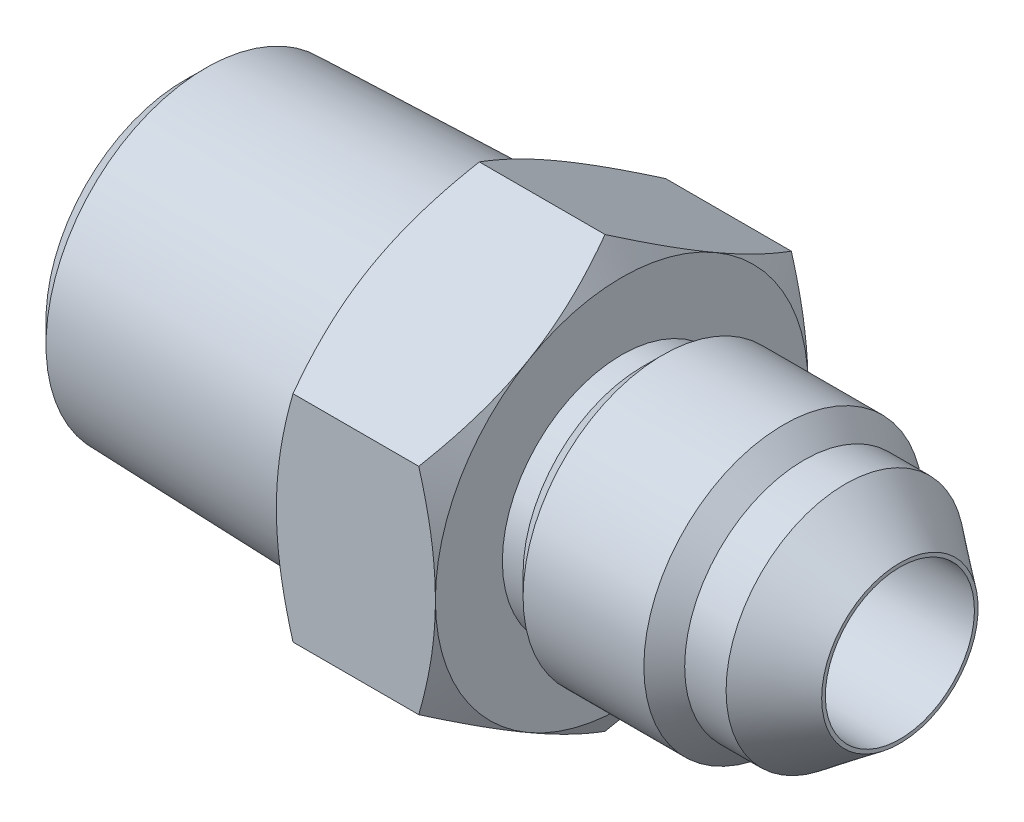
SolidWorks part; units mm, degrees
ref_plane "Front" through (0, 0, 0) normal (0, 0, 1) x (1, 0, 0)
ref_plane "Top" through (0, 0, 0) normal (0, 1, 0) x (1, 0, 0)
ref_plane "Right" through (0, 0, 0) normal (1, 0, 0) x (0, 0, -1)
sketch "Sketch6" plane through (0, 0, 0) normal (0, 0, 1) x (1, 0, 0)
  line L0 (-4.064, 8.5725) -> (-4.064, -8.5725) construction
  line L1 (18.288, 7.1438) -> (18.288, -7.1438) construction
  line L2 (-18.288, 0) -> (18.288, 0)
  line L4 (-18.288, 0) -> (-18.288, 7.1438)
  line L5 (-18.288, 7.1438) -> (18.288, 7.1438)
  line L6 (18.288, 0) -> (18.288, 7.1438)
  line L7 (-18.288, 3.81) -> (-18.288, -3.81) construction
  line L8 (-4.064, 10.287) -> (-4.064, -10.287) construction
  line L9 (4.064, 10.287) -> (4.064, -10.287) construction
  point P4 (4.064, 0)
  point P6 (-4.064, 0)
  dimension "Straight Dia" = 14.2875
  dimension "Length" = 36.576
  dimension "L1" = 14.224
  dimension "Pipe OD" = 17.145
  dimension "L2" = 14.224
  dimension "D1" = 7.62
  dimension "D2" = 20.574
revolve "Revolve3" add sketch "Sketch6" angle 360 about L2
sketch "Sketch14" plane through (18.288, 0, 0) normal (-1, 0, 0) x (0, 0, 1)
  circle A1 centre (0, 0) radius 7.1438
  circle A2 centre (0, 0) radius 7.1438
  dimension "D1" = 0
curve "Helix/Spiral1" pitch 1.4111 height 15.6351 turns 11.08 parameters "Pitch"=1.4111
sketch "Sketch15" plane through (0, 0, 0) normal (0, 0, 1) x (1, 0, 0)
  line L0 (18.288, 7.1438) -> (19.5227, 7.1438)
  line L1 (19.5227, 7.1438) -> (18.9936, 6.2272)
  line L2 (18.9936, 6.2272) -> (18.8172, 6.2272)
  line L3 (18.8172, 6.2272) -> (18.288, 7.1438)
  line L4 (18.9054, 6.2272) -> (18.9054, 7.1438) construction
  line L5 (18.5526, 6.6855) -> (19.2581, 6.6855) construction
  dimension "D1" = 60
  dimension "D2" = 0.1764
  dimension "D3" = 0.7056
sweep "Cut-Sweep1" [suppressed] cut profiles "Sketch15" path "Helix/Spiral1"
ref_plane "Plane1" through (-4.064, 0, 0) normal (1, 0, 0) x (0, 0, -1)
sketch "Sketch12" plane through (-4.064, 0, 0) normal (1, 0, 0) x (0, 0, -1)
  line L1 (0, 10.9985) -> (-9.525, 5.4993)
  line L2 (-9.525, 5.4993) -> (-9.525, -5.4993)
  line L3 (-9.525, -5.4993) -> (0, -10.9985)
  line L4 (0, -10.9985) -> (9.525, -5.4993)
  line L5 (9.525, -5.4993) -> (9.525, 5.4993)
  line L6 (9.525, 5.4993) -> (0, 10.9985)
  circle A0 centre (0, 0) radius 9.525 construction
  dimension "Hex" = 19.05
extrude "Extrude1" add sketch "Sketch12" along normal up to vertex (8.128 mm away) up to point (4.064, 0, 0)
sketch "Sketch7" plane through (0, 0, 0) normal (0, 0, 1) x (1, 0, 0)
  line L0 (-18.288, 0) -> (-18.288, 3.81)
  line L2 (-18.288, 3.81) -> (18.288, 3.81)
  line L4 (18.288, 0) -> (18.288, 7.1438) construction
  line L11 (18.288, 3.81) -> (18.288, 0)
  line L12 (18.288, 0) -> (-18.288, 0)
  line L13 (-18.288, 3.81) -> (-18.288, -3.81) construction
  dimension "ID" = 7.62
sketch "Sketch10" plane through (0, 0, 0) normal (0, 0, 1) x (1, 0, 0)
  line L0 (-18.288, 7.1438) -> (18.288, 7.1438) construction
  line L1 (18.288, 7.1438) -> (19.5227, 7.1438) construction
  line L2 (-4.064, -8.5725) -> (-18.288, -8.1378) construction
  line L3 (4.064, 10.9985) -> (4.064, 5.4993) construction
  line L5 (0, 0) -> (-18.288, 0) construction
  line L6 (6.1659, 7.1438) -> (4.064, 7.1438)
  line L9 (4.064, 6.1002) -> (4.064, 7.1438)
  line L21 (18.288, 7.1438) -> (12.3414, 7.1438)
  line L22 (12.3414, 7.1438) -> (13.3849, 6.1002)
  line L23 (13.3849, 6.1002) -> (15.5016, 6.1002)
  line L24 (15.5016, 6.1002) -> (18.288, 4.0005)
  line L25 (18.288, 4.0005) -> (18.288, 7.1438)
  line L26 (5.1223, 6.1002) -> (4.064, 6.1002)
  line L27 (6.1659, 7.1438) -> (5.1223, 6.1002)
  point P5 (10.5627, -7.1437)
  point P9 (-11.938, -8.3319)
  dimension "D1" = 8.001
  dimension "D2" = 37
  dimension "D3" = 2.1167
  dimension "D5" = 45
  dimension "D4" = 1.0583
  dimension "D6" = 2.8222
  dimension "D7" = 0.127
  dimension "D9" = 6.35
  dimension "D8" = 1.75
revolve "Cut-Revolve6" cut sketch "Sketch10" angle 360 about L2
revolve "Cut-Revolve5" cut sketch "Sketch7" angle 360 about L12
sketch "Sketch13" plane through (0, 0, 0) normal (0, 0, 1) x (1, 0, 0)
  line L0 (-4.064, 10.9985) -> (-4.064, 9.525)
  line L1 (-4.064, 5.4993) -> (-4.064, 10.9985) construction
  line L2 (-4.064, 9.525) -> (-3.2133, 10.9985)
  line L3 (-3.2133, 10.9985) -> (-4.064, 10.9985)
  line L4 (3.2133, 10.9985) -> (4.064, 9.525)
  line L5 (4.064, 10.9985) -> (4.064, 5.4993) construction
  line L6 (4.064, 9.525) -> (4.064, 10.9985)
  line L7 (4.064, 10.9985) -> (3.2133, 10.9985)
  dimension "D2" = 30
revolve "Cut-Revolve7" cut sketch "Sketch13" angle 360 about L2
sketch "Sketch17" plane through (-18.288, 0, 0) normal (-1, 0, 0) x (0, 0, 1)
  circle A0 centre (0, 0) radius 7.1438 construction
  circle A1 centre (0, 0) radius 7.1438
extrude "Cut-Extrude1" cut sketch "Sketch17" against normal up to vertex (14.224 mm away) up to point (-4.064, 0, 0)
ref_plane "Plane2" through (-4.064, 0, 0) normal (1, 0, 0) x (0, 0, -1)
sketch "Sketch19" plane through (-4.064, 0, 0) normal (1, 0, 0) x (0, 0, -1)
  circle A0 centre (0, 0) radius 8.5725
extrude "Boss-Extrude1" add sketch "Sketch19" against normal up to vertex (14.224 mm away) draft 1.75 separate body up to point (-18.288, 0, 0)
sketch "Sketch20" plane through (-18.288, 0, 0) normal (1, 0, 0) x (0, 0, -1)
  circle A1 centre (0, 0) radius 8.1379
  circle A2 centre (0, 0) radius 8.1379 construction
sketch "Sketch21" plane through (0, 0, 0) normal (0, 0, 1) x (1, 0, 0)
  line L0 (-19.4911, 8.0178) -> (-18.3573, 8.0178) construction
  line L1 (-19.6298, 8.258) -> (-18.9242, 7.036) construction
  line L2 (-19.0443, 7.244) -> (-18.8041, 7.244)
  line L3 (-18.9242, 7.036) -> (-18.2187, 8.258) construction
  line L4 (-18.9242, 7.036) -> (-18.8041, 7.244) construction
  line L5 (-18.9242, 8.0178) -> (-18.9242, 8.258) construction
  line L6 (-19.6298, 8.258) -> (-18.2187, 8.258) construction
  line L7 (-18.9242, 8.1379) -> (-18.288, 8.1379) construction
  line L8 (-18.2187, 8.258) -> (-19.5604, 8.1379)
  line L9 (-19.5604, 8.1379) -> (-19.0443, 7.244)
  line L10 (-18.8041, 7.244) -> (-18.2187, 8.258)
  line L11 (-18.9242, 7.036) -> (-18.9242, 7.244) construction
  dimension "D2" = 0.2402
  dimension "D1" = 1.4111
curve "Helix/Spiral2" parameters "Pitch"=1.4111
chamfer "Chamfer1" distance 1.0583 angle 45 1 edges at (-18.288, 0, -8.1379) first distance on face at (-18.288, 0, -8.1379)
sketch "Sketch22" plane through (-4.064, 0, 0) normal (1, 0, 0) x (0, 0, -1)
  circle A1 centre (0, 0) radius 8.5725
  circle A2 centre (0, 0) radius 8.5725
  dimension "D1" = 0
sweep "Cut-Sweep2" [suppressed] cut profiles "Sketch21" path "Helix/Spiral2"
extrude "Boss-Extrude3" add sketch "Sketch22" against normal up to vertex (14.224 mm away) draft 15 up to point (-18.288, 7.1438, 0)
combine bodies "Combine1" operation type add bodies to combine 173 169
sketch "Sketch23" plane through (-18.288, 0, 0) normal (-1, 0, 0) x (0, 0, 1)
  circle A2 centre (0, 0) radius 3.81
extrude "Cut-Extrude2" cut sketch "Sketch23" against normal up to vertex (14.224 mm away) up to point (-4.064, 0, 0)
other "CPoint1" parameters "Diameter"=9.525, "StubLength"=25.4
ref_axis "Axis1" through (28.288, 0, 0) along (-1, 0, 0)
equation "\"D3@Helix/Spiral1\" = \"L1@Sketch6\"+\"Pitch@Helix/Spiral1\""
equation "\"D2@Sketch15\" = \"Pitch@Helix/Spiral1\"*.125"
equation "\"D3@Sketch15\" = \"Pitch@Helix/Spiral1\"*.5"
equation "\"D3@Sketch10\" = \"Pitch@Helix/Spiral1\"*1.5"
equation "\"D1@Sketch10\" = \"ID@Sketch7\"*1.05"
equation "\"D1@Sketch21\" = \"Pitch@Helix/Spiral2\""
equation "\"D3@Helix/Spiral2\" = \"L2@Sketch6\"+\"Pitch@Helix/Spiral2\""
equation "\"D1@Chamfer1\" = \"Pitch@Helix/Spiral2\"*.75"
equation "\"D4@Sketch10\" = \"Pitch@Helix/Spiral1\"*.75"
equation "\"D6@Sketch10\" = \"Pitch@Helix/Spiral1\"*2"
equation "\"D9@Sketch10\" = \"Pitch@Helix/Spiral2\"*4.5"
equation "\"D2@Sketch6\" = \"Hex@Sketch12\"+.06"
